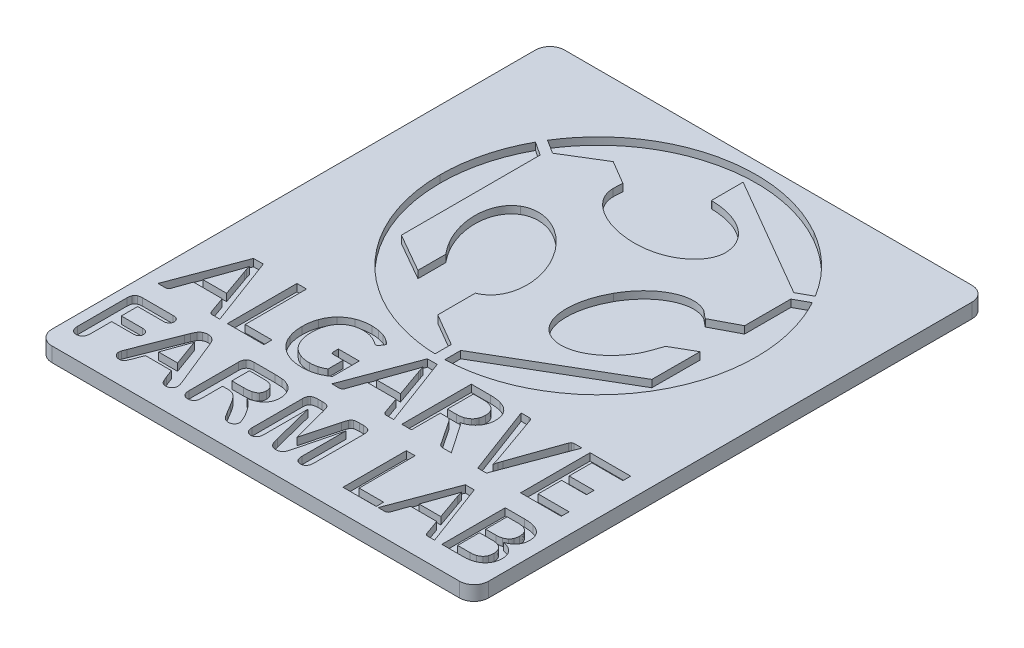
SolidWorks part; units mm, degrees
ref_plane "Front Plane" through (0, 0, 0) normal (0, 0, 1) x (1, 0, 0)
ref_plane "Top Plane" through (0, 0, 0) normal (0, 1, 0) x (1, 0, 0)
ref_plane "Right Plane" through (0, 0, 0) normal (1, 0, 0) x (0, 0, -1)
sketch "Sketch2" plane through (0, 0, 0) normal (0, 1, 0) x (1, 0, 0)
  line L0 (131.5064, 305.804) -> (131.5064, 308.3921)
  line L1 (128.174, 309.6973) -> (128.174, 307.7746)
  line L2 (128.174, 307.7746) -> (125.5144, 309.2966)
  line L3 (125.5144, 309.2966) -> (125.5144, 318.8292)
  line L4 (125.5144, 318.8292) -> (124.5822, 319.4445)
  line L5 (133.7323, 303.3878) -> (133.7333, 304.5062)
  line L6 (133.7333, 304.5062) -> (131.5064, 305.804)
  line L7 (128.4175, 320.9514) -> (130.0431, 319.988)
  line L8 (132.4676, 321.8251) -> (131.2821, 322.5835)
  line L9 (131.2821, 322.5835) -> (134.1018, 324.1923)
  line L10 (134.1018, 324.1923) -> (142.414, 319.3606)
  line L11 (142.414, 319.3606) -> (143.3673, 319.8839)
  line L12 (124.8866, 319.9657) -> (125.8322, 319.3686)
  line L13 (125.8322, 319.3686) -> (128.4175, 320.9514)
  line L14 (142.6945, 315.6997) -> (140.9269, 314.7758)
  line L15 (141.2046, 311.7531) -> (142.7105, 312.6237)
  line L16 (142.7105, 312.6237) -> (142.7015, 309.3183)
  line L17 (142.7015, 309.3183) -> (134.4115, 304.4769)
  line L18 (134.4115, 304.4769) -> (134.4155, 303.3861)
  line L19 (143.648, 319.3955) -> (142.6945, 318.8719)
  line L20 (142.6945, 318.8719) -> (142.6945, 315.6997)
  line L21 (122.4512, 295.9899) -> (120.7008, 295.9899)
  line L22 (120.7008, 295.9899) -> (120.7008, 294.8679)
  line L23 (120.7008, 294.8679) -> (122.1639, 294.8679)
  line L24 (122.1639, 294.2006) -> (120.7008, 294.2006)
  line L25 (120.7008, 294.2006) -> (120.7008, 292.7555)
  line L26 (119.8122, 292.7555) -> (119.8122, 296.1305)
  line L27 (120.3567, 296.675) -> (122.4512, 296.675)
  line L28 (125.88, 292.7854) -> (125.6706, 293.3359)
  line L29 (125.6706, 293.3359) -> (123.8873, 293.3359)
  line L30 (123.8873, 293.3359) -> (123.6779, 292.7734)
  line L31 (122.888, 293.0667) -> (124.01, 295.9151)
  line L32 (125.5479, 295.9211) -> (126.6939, 293.0906)
  line L33 (124.1207, 294.0032) -> (125.4312, 294.0032)
  line L34 (125.4312, 294.0032) -> (124.77, 295.8133)
  line L35 (124.77, 295.8133) -> (124.1207, 294.0032)
  line L36 (128.6716, 294.1647) -> (128.3604, 294.1647)
  line L37 (128.3604, 294.1647) -> (128.3604, 292.7555)
  line L38 (127.4718, 292.7555) -> (127.4718, 296.1305)
  line L39 (128.0163, 296.675) -> (129.4615, 296.675)
  line L40 (130.0689, 292.7794) -> (129.7128, 293.3719)
  line L41 (129.1802, 296.0078) -> (128.3604, 296.0078)
  line L42 (128.3604, 296.0078) -> (128.3604, 294.802)
  line L43 (128.3604, 294.802) -> (129.1563, 294.802)
  line L44 (133.3631, 292.95) -> (132.66, 295.7445)
  line L45 (132.66, 295.7445) -> (132.66, 292.7166)
  line L46 (131.8431, 292.7166) -> (131.8431, 296.1873)
  line L47 (132.3967, 296.675) -> (132.6719, 296.675)
  line L48 (133.3212, 296.0886) -> (133.9585, 293.686)
  line L49 (133.9585, 293.686) -> (134.5958, 296.0886)
  line L50 (135.2451, 296.675) -> (135.5203, 296.675)
  line L51 (136.0739, 296.1873) -> (136.0739, 292.7166)
  line L52 (135.257, 292.7166) -> (135.257, 295.7445)
  line L53 (135.257, 295.7445) -> (134.5539, 292.95)
  line L54 (139.1121, 292.7958) -> (140.7924, 292.7958)
  line L55 (140.7924, 292.7958) -> (140.7924, 292.2887)
  line L56 (140.7924, 292.2887) -> (138.5089, 292.2887)
  line L57 (138.5089, 292.2887) -> (138.5089, 296.6437)
  line L58 (138.5089, 296.6437) -> (139.1121, 296.6437)
  line L59 (139.1121, 296.6437) -> (139.1121, 292.7958)
  line L60 (144.8059, 292.2887) -> (144.3386, 292.2887)
  line L61 (144.1365, 292.4279) -> (143.7653, 293.4752)
  line L62 (143.7653, 293.4752) -> (141.9689, 293.4752)
  line L63 (141.9689, 293.4752) -> (141.6011, 292.4313)
  line L64 (141.3956, 292.2887) -> (140.9283, 292.2887)
  line L65 (140.9283, 292.2887) -> (142.5622, 296.6437)
  line L66 (142.5622, 296.6437) -> (143.1753, 296.6437)
  line L67 (143.1753, 296.6437) -> (144.8059, 292.2887)
  line L68 (142.1214, 293.9061) -> (143.6128, 293.9061)
  line L69 (143.6128, 293.9061) -> (142.9964, 295.6593)
  line L70 (142.7378, 295.656) -> (142.1214, 293.9061)
  line L71 (145.3031, 292.2887) -> (145.3031, 296.6437)
  line L72 (145.3031, 296.6437) -> (146.6321, 296.6437)
  line L73 (146.7746, 292.2887) -> (145.3031, 292.2887)
  line L74 (145.9063, 294.2707) -> (145.9063, 292.766)
  line L75 (145.9063, 292.766) -> (146.7647, 292.766)
  line L76 (146.7647, 294.2707) -> (145.9063, 294.2707)
  line L77 (145.9063, 294.6949) -> (146.6089, 294.6949)
  line L78 (146.6321, 296.1697) -> (145.9063, 296.1697)
  line L79 (145.9063, 296.1697) -> (145.9063, 294.6949)
  line L80 (124.2771, 298.0591) -> (123.7647, 298.0591)
  line L81 (123.543, 298.2117) -> (123.136, 299.3601)
  line L82 (123.136, 299.3601) -> (121.1664, 299.3601)
  line L83 (121.1664, 299.3601) -> (120.763, 298.2153)
  line L84 (120.5377, 298.0591) -> (120.0253, 298.0591)
  line L85 (120.0253, 298.0591) -> (121.8169, 302.8342)
  line L86 (121.8169, 302.8342) -> (122.4892, 302.8342)
  line L87 (122.4892, 302.8342) -> (124.2771, 298.0591)
  line L88 (121.3336, 299.8325) -> (122.9689, 299.8325)
  line L89 (122.9689, 299.8325) -> (122.2929, 301.7549)
  line L90 (122.0095, 301.7513) -> (121.3336, 299.8325)
  line L91 (125.4618, 298.6151) -> (127.3043, 298.6151)
  line L92 (127.3043, 298.6151) -> (127.3043, 298.0591)
  line L93 (127.3043, 298.0591) -> (124.8004, 298.0591)
  line L94 (124.8004, 298.0591) -> (124.8004, 302.8342)
  line L95 (124.8004, 302.8342) -> (125.4618, 302.8342)
  line L96 (125.4618, 302.8342) -> (125.4618, 298.6151)
  line L97 (131.5161, 302.2855) -> (131.3308, 301.9875)
  line L98 (130.9565, 298.8113) -> (130.9565, 299.8579)
  line L99 (130.9565, 299.8579) -> (130.2697, 299.8579)
  line L100 (130.1243, 299.9851) -> (130.1243, 300.3594)
  line L101 (130.1243, 300.3594) -> (131.5561, 300.3594)
  line L102 (131.5561, 300.3594) -> (131.5561, 298.5206)
  line L103 (136.2258, 298.0591) -> (135.7134, 298.0591)
  line L104 (135.4918, 298.2117) -> (135.0848, 299.3601)
  line L105 (135.0848, 299.3601) -> (133.1151, 299.3601)
  line L106 (133.1151, 299.3601) -> (132.7117, 298.2153)
  line L107 (132.4864, 298.0591) -> (131.974, 298.0591)
  line L108 (131.974, 298.0591) -> (133.7656, 302.8342)
  line L109 (133.7656, 302.8342) -> (134.4379, 302.8342)
  line L110 (134.4379, 302.8342) -> (136.2258, 298.0591)
  line L111 (133.2823, 299.8325) -> (134.9176, 299.8325)
  line L112 (134.9176, 299.8325) -> (134.2417, 301.7549)
  line L113 (133.9582, 301.7513) -> (133.2823, 299.8325)
  line L114 (137.4433, 300.0433) -> (137.4433, 298.0591)
  line L115 (137.4433, 298.0591) -> (136.7819, 298.0591)
  line L116 (136.7819, 298.0591) -> (136.7819, 302.8342)
  line L117 (136.7819, 302.8342) -> (138.0901, 302.8342)
  line L118 (138.8969, 299.9488) -> (140.1797, 298.0591)
  line L119 (140.1797, 298.0591) -> (139.591, 298.0591)
  line L120 (139.3257, 298.1935) -> (138.1955, 299.8943)
  line L121 (137.8866, 300.0433) -> (137.4433, 300.0433)
  line L122 (137.4433, 300.5266) -> (138.0647, 300.5266)
  line L123 (138.0901, 302.3145) -> (137.4433, 302.3145)
  line L124 (137.4433, 302.3145) -> (137.4433, 300.5266)
  line L125 (140.2088, 302.8342) -> (140.743, 302.8342)
  line L126 (140.9646, 302.6816) -> (142.1457, 299.3346)
  line L127 (142.4546, 299.3346) -> (143.632, 302.6779)
  line L128 (143.8537, 302.8342) -> (144.3879, 302.8342)
  line L129 (144.3879, 302.8342) -> (142.5963, 298.0591)
  line L130 (142.5963, 298.0591) -> (142.0003, 298.0591)
  line L131 (142.0003, 298.0591) -> (140.2088, 302.8342)
  line L132 (147.7349, 302.8342) -> (147.7349, 302.2964)
  line L133 (147.7349, 302.2964) -> (145.6089, 302.2964)
  line L134 (145.6089, 302.2964) -> (145.6089, 300.7301)
  line L135 (145.6089, 300.7301) -> (147.3206, 300.7301)
  line L136 (147.3206, 300.7301) -> (147.3206, 300.2104)
  line L137 (147.3206, 300.2104) -> (145.6089, 300.2104)
  line L138 (145.6089, 300.2104) -> (145.6089, 298.5969)
  line L139 (145.6089, 298.5969) -> (147.7385, 298.5969)
  line L140 (147.7385, 298.5969) -> (147.7349, 298.0591)
  line L141 (147.7349, 298.0591) -> (144.9439, 298.0591)
  line L142 (144.9439, 298.0591) -> (144.9439, 302.8342)
  line L143 (144.9439, 302.8342) -> (147.7349, 302.8342)
  line L144 (134.1018, 324.1923) -> (134.1018, 302.8342) construction
  line L146 (120.1018, 325.9189) -> (148.1018, 325.9189)
  line L147 (119.1018, 324.9189) -> (119.1018, 291.7017)
  line L148 (120.1018, 290.7017) -> (148.1018, 290.7017)
  line L149 (149.1018, 324.9189) -> (149.1018, 291.7017)
  arc A0 (148.1018, 325.9189) -> (149.1018, 324.9189) centre (148.1018, 324.9189) cw
  arc A1 (148.1018, 290.7017) -> (149.1018, 291.7017) centre (148.1018, 291.7017) ccw
  arc A2 (119.1018, 291.7017) -> (120.1018, 290.7017) centre (120.1018, 291.7017) ccw
  arc A3 (120.1018, 325.9189) -> (119.1018, 324.9189) centre (120.1018, 324.9189) ccw
  spline S0 degree 3 poles (131.5064, 308.3921) (131.5993, 308.4277) (131.6899, 308.4701) (131.7769, 308.5214) knots 0 0 0 0 1 1 1 1
  spline S1 degree 3 poles (131.7769, 308.5214) (133.0109, 309.2489) (133.1406, 311.3156) (132.0664, 313.1373) knots 0 0 0 0 1 1 1 1
  spline S2 degree 3 poles (132.0664, 313.1373) (130.9923, 314.959) (129.1213, 315.846) (127.8874, 315.1185) knots 0 0 0 0 1 1 1 1
  spline S3 degree 3 poles (127.8874, 315.1185) (126.6534, 314.3909) (126.5238, 312.3243) (127.5977, 310.5026) knots 0 0 0 0 1 1 1 1
  spline S4 degree 3 poles (127.5977, 310.5026) (127.771, 310.2088) (127.9652, 309.9397) (128.174, 309.6973) knots 0 0 0 0 1 1 1 1
  spline S5 degree 3 poles (124.5822, 319.4445) (123.733, 317.8973) (123.2501, 316.1206) (123.2501, 314.2311) knots 0 0 0 0 1 1 1 1
  spline S6 degree 3 poles (123.2501, 314.2311) (123.2501, 308.3603) (127.9085, 303.5807) (133.7323, 303.3878) knots 0 0 0 0 1 1 1 1
  spline S7 degree 3 poles (130.0431, 319.988) (130.011, 319.7209) (130.01, 319.4269) (130.011, 319.3258) knots 0 0 0 0 1 1 1 1
  spline S8 degree 3 poles (130.011, 319.3258) (130.0259, 317.8934) (131.9657, 316.8046) (134.0804, 316.8265) knots 0 0 0 0 1 1 1 1
  spline S9 degree 3 poles (134.0804, 316.8265) (136.1951, 316.8484) (137.7012, 318.1295) (137.6905, 319.3899) knots 0 0 0 0 1 1 1 1
  spline S10 degree 3 poles (137.6905, 319.3899) (137.6784, 320.8222) (136.3011, 321.9436) (134.1872, 322.0066) knots 0 0 0 0 1 1 1 1
  spline S11 degree 3 poles (134.1872, 322.0066) (133.4716, 322.028) (132.7817, 321.8851) (132.4676, 321.8251) knots 0 0 0 0 1 1 1 1
  spline S12 degree 3 poles (143.3673, 319.8839) (142.4502, 321.3918) (141.1514, 322.6968) (139.5139, 323.6396) knots 0 0 0 0 1 1 1 1
  spline S13 degree 3 poles (139.5139, 323.6396) (134.426, 326.5689) (127.9596, 324.9166) (124.8866, 319.9657) knots 0 0 0 0 1 1 1 1
  spline S14 degree 3 poles (140.9269, 314.7758) (140.8628, 314.7865) (140.4704, 315.1537) (140.3822, 315.203) knots 0 0 0 0 1 1 1 1
  spline S15 degree 3 poles (140.3822, 315.203) (139.1308, 315.9002) (137.2885, 314.9784) (136.2593, 313.131) knots 0 0 0 0 1 1 1 1
  spline S16 degree 3 poles (136.2593, 313.131) (135.2301, 311.2837) (135.3178, 309.1714) (136.5691, 308.4742) knots 0 0 0 0 1 1 1 1
  spline S17 degree 3 poles (136.5691, 308.4742) (137.8205, 307.7771) (139.6839, 308.6134) (140.7132, 310.4608) knots 0 0 0 0 1 1 1 1
  spline S18 degree 3 poles (140.7132, 310.4608) (140.8792, 310.7588) (141.1009, 311.4506) (141.2046, 311.7531) knots 0 0 0 0 1 1 1 1
  spline S19 degree 3 poles (134.4155, 303.3861) (136.1798, 303.435) (137.9571, 303.9162) (139.5876, 304.8709) knots 0 0 0 0 1 1 1 1
  spline S20 degree 3 poles (139.5876, 304.8709) (144.6537, 307.8374) (146.4243, 314.2724) (143.648, 319.3955) knots 0 0 0 0 1 1 1 1
  spline S21 degree 3 poles (122.1639, 294.8679) (122.2996, 294.8679) (122.4003, 294.8369) (122.4661, 294.7751) knots 0 0 0 0 1 1 1 1
  spline S22 degree 3 poles (122.4661, 294.7751) (122.5339, 294.7153) (122.5679, 294.6345) (122.5679, 294.5328) knots 0 0 0 0 1 1 1 1
  spline S23 degree 3 poles (122.5679, 294.5328) (122.5679, 294.431) (122.5339, 294.3502) (122.4661, 294.2904) knots 0 0 0 0 1 1 1 1
  spline S24 degree 3 poles (122.4661, 294.2904) (122.3983, 294.2306) (122.2976, 294.2006) (122.1639, 294.2006) knots 0 0 0 0 1 1 1 1
  spline S25 degree 3 poles (120.7008, 292.7555) (120.7008, 292.572) (120.6589, 292.4353) (120.5752, 292.3456) knots 0 0 0 0 1 1 1 1
  spline S26 degree 3 poles (120.5752, 292.3456) (120.4934, 292.2578) (120.3877, 292.2139) (120.258, 292.2139) knots 0 0 0 0 1 1 1 1
  spline S27 degree 3 poles (120.258, 292.2139) (120.1264, 292.2139) (120.0187, 292.2588) (119.9349, 292.3486) knots 0 0 0 0 1 1 1 1
  spline S28 degree 3 poles (119.9349, 292.3486) (119.8531, 292.4383) (119.8122, 292.574) (119.8122, 292.7555) knots 0 0 0 0 1 1 1 1
  spline S29 degree 3 poles (119.8122, 296.1305) (119.8122, 296.2582) (119.8312, 296.3619) (119.869, 296.4417) knots 0 0 0 0 1 1 1 1
  spline S30 degree 3 poles (119.869, 296.4417) (119.9069, 296.5235) (119.9658, 296.5823) (120.0456, 296.6182) knots 0 0 0 0 1 1 1 1
  spline S31 degree 3 poles (120.0456, 296.6182) (120.1274, 296.6561) (120.2311, 296.675) (120.3567, 296.675) knots 0 0 0 0 1 1 1 1
  spline S32 degree 3 poles (122.4512, 296.675) (122.5928, 296.675) (122.6975, 296.6431) (122.7653, 296.5793) knots 0 0 0 0 1 1 1 1
  spline S33 degree 3 poles (122.7653, 296.5793) (122.8351, 296.5175) (122.8701, 296.4357) (122.8701, 296.334) knots 0 0 0 0 1 1 1 1
  spline S34 degree 3 poles (122.8701, 296.334) (122.8701, 296.2302) (122.8351, 296.1465) (122.7653, 296.0826) knots 0 0 0 0 1 1 1 1
  spline S35 degree 3 poles (122.7653, 296.0826) (122.6975, 296.0208) (122.5928, 295.9899) (122.4512, 295.9899) knots 0 0 0 0 1 1 1 1
  spline S36 degree 3 poles (123.6779, 292.7734) (123.5961, 292.554) (123.5263, 292.4054) (123.4685, 292.3276) knots 0 0 0 0 1 1 1 1
  spline S37 degree 3 poles (123.4685, 292.3276) (123.4106, 292.2518) (123.3159, 292.2139) (123.1842, 292.2139) knots 0 0 0 0 1 1 1 1
  spline S38 degree 3 poles (123.1842, 292.2139) (123.0725, 292.2139) (122.9738, 292.2548) (122.888, 292.3366) knots 0 0 0 0 1 1 1 1
  spline S39 degree 3 poles (122.888, 292.3366) (122.8022, 292.4184) (122.7593, 292.5111) (122.7593, 292.6149) knots 0 0 0 0 1 1 1 1
  spline S40 degree 3 poles (122.7593, 292.6149) (122.7593, 292.6747) (122.7693, 292.7365) (122.7893, 292.8004) knots 0 0 0 0 1 1 1 1
  spline S41 degree 3 poles (122.7893, 292.8004) (122.8092, 292.8642) (122.8421, 292.953) (122.888, 293.0667) knots 0 0 0 0 1 1 1 1
  spline S42 degree 3 poles (124.01, 295.9151) (124.0419, 295.9969) (124.0798, 296.0946) (124.1237, 296.2083) knots 0 0 0 0 1 1 1 1
  spline S43 degree 3 poles (124.1237, 296.2083) (124.1696, 296.324) (124.2175, 296.4197) (124.2673, 296.4955) knots 0 0 0 0 1 1 1 1
  spline S44 degree 3 poles (124.2673, 296.4955) (124.3192, 296.5713) (124.386, 296.6322) (124.4678, 296.678) knots 0 0 0 0 1 1 1 1
  spline S45 degree 3 poles (124.4678, 296.678) (124.5516, 296.7259) (124.6543, 296.7498) (124.776, 296.7498) knots 0 0 0 0 1 1 1 1
  spline S46 degree 3 poles (124.776, 296.7498) (124.8996, 296.7498) (125.0024, 296.7259) (125.0842, 296.678) knots 0 0 0 0 1 1 1 1
  spline S47 degree 3 poles (125.0842, 296.678) (125.1679, 296.6322) (125.2347, 296.5723) (125.2846, 296.4985) knots 0 0 0 0 1 1 1 1
  spline S48 degree 3 poles (125.2846, 296.4985) (125.3365, 296.4247) (125.3794, 296.3449) (125.4133, 296.2592) knots 0 0 0 0 1 1 1 1
  spline S49 degree 3 poles (125.4133, 296.2592) (125.4492, 296.1754) (125.4941, 296.0627) (125.5479, 295.9211) knots 0 0 0 0 1 1 1 1
  spline S50 degree 3 poles (126.6939, 293.0906) (126.7836, 292.8752) (126.8285, 292.7186) (126.8285, 292.6209) knots 0 0 0 0 1 1 1 1
  spline S51 degree 3 poles (126.8285, 292.6209) (126.8285, 292.5191) (126.7856, 292.4254) (126.6998, 292.3396) knots 0 0 0 0 1 1 1 1
  spline S52 degree 3 poles (126.6998, 292.3396) (126.6161, 292.2558) (126.5143, 292.2139) (126.3947, 292.2139) knots 0 0 0 0 1 1 1 1
  spline S53 degree 3 poles (126.3947, 292.2139) (126.3248, 292.2139) (126.265, 292.2269) (126.2151, 292.2528) knots 0 0 0 0 1 1 1 1
  spline S54 degree 3 poles (126.2151, 292.2528) (126.1653, 292.2768) (126.1234, 292.3097) (126.0895, 292.3516) knots 0 0 0 0 1 1 1 1
  spline S55 degree 3 poles (126.0895, 292.3516) (126.0556, 292.3955) (126.0187, 292.4613) (125.9788, 292.549) knots 0 0 0 0 1 1 1 1
  spline S56 degree 3 poles (125.9788, 292.549) (125.9409, 292.6388) (125.908, 292.7176) (125.88, 292.7854) knots 0 0 0 0 1 1 1 1
  spline S57 degree 3 poles (128.3604, 292.7555) (128.3604, 292.57) (128.3195, 292.4334) (128.2377, 292.3456) knots 0 0 0 0 1 1 1 1
  spline S58 degree 3 poles (128.2377, 292.3456) (128.156, 292.2578) (128.0492, 292.2139) (127.9176, 292.2139) knots 0 0 0 0 1 1 1 1
  spline S59 degree 3 poles (127.9176, 292.2139) (127.776, 292.2139) (127.6663, 292.2598) (127.5885, 292.3516) knots 0 0 0 0 1 1 1 1
  spline S60 degree 3 poles (127.5885, 292.3516) (127.5107, 292.4433) (127.4718, 292.578) (127.4718, 292.7555) knots 0 0 0 0 1 1 1 1
  spline S61 degree 3 poles (127.4718, 296.1305) (127.4718, 296.322) (127.5147, 296.4606) (127.6004, 296.5464) knots 0 0 0 0 1 1 1 1
  spline S62 degree 3 poles (127.6004, 296.5464) (127.6862, 296.6322) (127.8248, 296.675) (128.0163, 296.675) knots 0 0 0 0 1 1 1 1
  spline S63 degree 3 poles (129.4615, 296.675) (129.661, 296.675) (129.8315, 296.6661) (129.9731, 296.6481) knots 0 0 0 0 1 1 1 1
  spline S64 degree 3 poles (129.9731, 296.6481) (130.1147, 296.6322) (130.2424, 296.5983) (130.3561, 296.5464) knots 0 0 0 0 1 1 1 1
  spline S65 degree 3 poles (130.3561, 296.5464) (130.4937, 296.4885) (130.6154, 296.4058) (130.7211, 296.2981) knots 0 0 0 0 1 1 1 1
  spline S66 degree 3 poles (130.7211, 296.2981) (130.8268, 296.1903) (130.9066, 296.0647) (130.9605, 295.9211) knots 0 0 0 0 1 1 1 1
  spline S67 degree 3 poles (130.9605, 295.9211) (131.0163, 295.7794) (131.0443, 295.6288) (131.0443, 295.4693) knots 0 0 0 0 1 1 1 1
  spline S68 degree 3 poles (131.0443, 295.4693) (131.0443, 295.1421) (130.9515, 294.8808) (130.766, 294.6854) knots 0 0 0 0 1 1 1 1
  spline S69 degree 3 poles (130.766, 294.6854) (130.5825, 294.4899) (130.3032, 294.3512) (129.9282, 294.2695) knots 0 0 0 0 1 1 1 1
  spline S70 degree 3 poles (129.9282, 294.2695) (130.0858, 294.1857) (130.2364, 294.062) (130.38, 293.8984) knots 0 0 0 0 1 1 1 1
  spline S71 degree 3 poles (130.38, 293.8984) (130.5237, 293.7349) (130.6513, 293.5603) (130.763, 293.3748) knots 0 0 0 0 1 1 1 1
  spline S72 degree 3 poles (130.763, 293.3748) (130.8767, 293.1913) (130.9645, 293.0248) (131.0263, 292.8752) knots 0 0 0 0 1 1 1 1
  spline S73 degree 3 poles (131.0263, 292.8752) (131.0901, 292.7276) (131.1221, 292.6258) (131.1221, 292.57) knots 0 0 0 0 1 1 1 1
  spline S74 degree 3 poles (131.1221, 292.57) (131.1221, 292.5121) (131.1031, 292.4543) (131.0652, 292.3965) knots 0 0 0 0 1 1 1 1
  spline S75 degree 3 poles (131.0652, 292.3965) (131.0293, 292.3406) (130.9794, 292.2967) (130.9156, 292.2648) knots 0 0 0 0 1 1 1 1
  spline S76 degree 3 poles (130.9156, 292.2648) (130.8518, 292.2309) (130.778, 292.2139) (130.6942, 292.2139) knots 0 0 0 0 1 1 1 1
  spline S77 degree 3 poles (130.6942, 292.2139) (130.5945, 292.2139) (130.5107, 292.2379) (130.4429, 292.2857) knots 0 0 0 0 1 1 1 1
  spline S78 degree 3 poles (130.4429, 292.2857) (130.3751, 292.3316) (130.3162, 292.3905) (130.2663, 292.4623) knots 0 0 0 0 1 1 1 1
  spline S79 degree 3 poles (130.2663, 292.4623) (130.2185, 292.5341) (130.1526, 292.6398) (130.0689, 292.7794) knots 0 0 0 0 1 1 1 1
  spline S80 degree 3 poles (129.7128, 293.3719) (129.5852, 293.5893) (129.4705, 293.7548) (129.3687, 293.8685) knots 0 0 0 0 1 1 1 1
  spline S81 degree 3 poles (129.3687, 293.8685) (129.269, 293.9822) (129.1673, 294.06) (129.0635, 294.1019) knots 0 0 0 0 1 1 1 1
  spline S82 degree 3 poles (129.0635, 294.1019) (128.9598, 294.1438) (128.8292, 294.1647) (128.6716, 294.1647) knots 0 0 0 0 1 1 1 1
  spline S83 degree 3 poles (129.1563, 294.802) (129.3697, 294.802) (129.5493, 294.82) (129.6949, 294.8559) knots 0 0 0 0 1 1 1 1
  spline S84 degree 3 poles (129.6949, 294.8559) (129.8405, 294.8938) (129.9512, 294.9566) (130.027, 295.0444) knots 0 0 0 0 1 1 1 1
  spline S85 degree 3 poles (130.027, 295.0444) (130.1048, 295.1342) (130.1437, 295.2568) (130.1437, 295.4124) knots 0 0 0 0 1 1 1 1
  spline S86 degree 3 poles (130.1437, 295.4124) (130.1437, 295.5341) (130.1128, 295.6408) (130.0509, 295.7326) knots 0 0 0 0 1 1 1 1
  spline S87 degree 3 poles (130.0509, 295.7326) (129.9891, 295.8263) (129.9033, 295.8961) (129.7936, 295.942) knots 0 0 0 0 1 1 1 1
  spline S88 degree 3 poles (129.7936, 295.942) (129.6899, 295.9859) (129.4854, 296.0078) (129.1802, 296.0078) knots 0 0 0 0 1 1 1 1
  spline S89 degree 3 poles (132.66, 292.7166) (132.66, 292.549) (132.6221, 292.4234) (132.5463, 292.3396) knots 0 0 0 0 1 1 1 1
  spline S90 degree 3 poles (132.5463, 292.3396) (132.4725, 292.2558) (132.3737, 292.2139) (132.2501, 292.2139) knots 0 0 0 0 1 1 1 1
  spline S91 degree 3 poles (132.2501, 292.2139) (132.1304, 292.2139) (132.0326, 292.2548) (131.9568, 292.3366) knots 0 0 0 0 1 1 1 1
  spline S92 degree 3 poles (131.9568, 292.3366) (131.881, 292.4204) (131.8431, 292.547) (131.8431, 292.7166) knots 0 0 0 0 1 1 1 1
  spline S93 degree 3 poles (131.8431, 296.1873) (131.8431, 296.3788) (131.893, 296.5075) (131.9927, 296.5733) knots 0 0 0 0 1 1 1 1
  spline S94 degree 3 poles (131.9927, 296.5733) (132.0925, 296.6411) (132.2271, 296.675) (132.3967, 296.675) knots 0 0 0 0 1 1 1 1
  spline S95 degree 3 poles (132.6719, 296.675) (132.8375, 296.675) (132.9572, 296.6601) (133.031, 296.6302) knots 0 0 0 0 1 1 1 1
  spline S96 degree 3 poles (133.031, 296.6302) (133.1068, 296.6002) (133.1626, 296.5464) (133.1985, 296.4686) knots 0 0 0 0 1 1 1 1
  spline S97 degree 3 poles (133.1985, 296.4686) (133.2344, 296.3908) (133.2753, 296.2641) (133.3212, 296.0886) knots 0 0 0 0 1 1 1 1
  spline S98 degree 3 poles (134.5958, 296.0886) (134.6417, 296.2641) (134.6826, 296.3908) (134.7185, 296.4686) knots 0 0 0 0 1 1 1 1
  spline S99 degree 3 poles (134.7185, 296.4686) (134.7544, 296.5464) (134.8092, 296.6002) (134.883, 296.6302) knots 0 0 0 0 1 1 1 1
  spline S100 degree 3 poles (134.883, 296.6302) (134.9588, 296.6601) (135.0795, 296.675) (135.2451, 296.675) knots 0 0 0 0 1 1 1 1
  spline S101 degree 3 poles (135.5203, 296.675) (135.6899, 296.675) (135.8245, 296.6411) (135.9243, 296.5733) knots 0 0 0 0 1 1 1 1
  spline S102 degree 3 poles (135.9243, 296.5733) (136.024, 296.5075) (136.0739, 296.3788) (136.0739, 296.1873) knots 0 0 0 0 1 1 1 1
  spline S103 degree 3 poles (136.0739, 292.7166) (136.0739, 292.549) (136.036, 292.4234) (135.9602, 292.3396) knots 0 0 0 0 1 1 1 1
  spline S104 degree 3 poles (135.9602, 292.3396) (135.8864, 292.2558) (135.7866, 292.2139) (135.661, 292.2139) knots 0 0 0 0 1 1 1 1
  spline S105 degree 3 poles (135.661, 292.2139) (135.5433, 292.2139) (135.4465, 292.2558) (135.3707, 292.3396) knots 0 0 0 0 1 1 1 1
  spline S106 degree 3 poles (135.3707, 292.3396) (135.2949, 292.4234) (135.257, 292.549) (135.257, 292.7166) knots 0 0 0 0 1 1 1 1
  spline S107 degree 3 poles (134.5539, 292.95) (134.508, 292.7685) (134.4701, 292.6348) (134.4402, 292.549) knots 0 0 0 0 1 1 1 1
  spline S108 degree 3 poles (134.4402, 292.549) (134.4123, 292.4653) (134.3594, 292.3885) (134.2816, 292.3187) knots 0 0 0 0 1 1 1 1
  spline S109 degree 3 poles (134.2816, 292.3187) (134.2038, 292.2488) (134.0961, 292.2139) (133.9585, 292.2139) knots 0 0 0 0 1 1 1 1
  spline S110 degree 3 poles (133.9585, 292.2139) (133.8548, 292.2139) (133.767, 292.2369) (133.6952, 292.2828) knots 0 0 0 0 1 1 1 1
  spline S111 degree 3 poles (133.6952, 292.2828) (133.6234, 292.3266) (133.5675, 292.3835) (133.5276, 292.4533) knots 0 0 0 0 1 1 1 1
  spline S112 degree 3 poles (133.5276, 292.4533) (133.4878, 292.5231) (133.4558, 292.5999) (133.4319, 292.6837) knots 0 0 0 0 1 1 1 1
  spline S113 degree 3 poles (133.4319, 292.6837) (133.41, 292.7695) (133.387, 292.8582) (133.3631, 292.95) knots 0 0 0 0 1 1 1 1
  spline S114 degree 3 poles (144.3386, 292.2887) (144.2856, 292.2887) (144.2425, 292.302) (144.2094, 292.3285) knots 0 0 0 0 1 1 1 1
  spline S115 degree 3 poles (144.2094, 292.3285) (144.1784, 292.355) (144.1541, 292.3882) (144.1365, 292.4279) knots 0 0 0 0 1 1 1 1
  spline S116 degree 3 poles (141.6011, 292.4313) (141.5878, 292.3937) (141.5624, 292.3605) (141.5248, 292.3318) knots 0 0 0 0 1 1 1 1
  spline S117 degree 3 poles (141.5248, 292.3318) (141.4895, 292.3031) (141.4464, 292.2887) (141.3956, 292.2887) knots 0 0 0 0 1 1 1 1
  spline S118 degree 3 poles (142.9964, 295.6593) (142.9743, 295.7124) (142.9522, 295.7742) (142.9301, 295.8449) knots 0 0 0 0 1 1 1 1
  spline S119 degree 3 poles (142.9301, 295.8449) (142.908, 295.9156) (142.887, 295.9919) (142.8671, 296.0736) knots 0 0 0 0 1 1 1 1
  spline S120 degree 3 poles (142.8671, 296.0736) (142.845, 295.9896) (142.8229, 295.9123) (142.8008, 295.8416) knots 0 0 0 0 1 1 1 1
  spline S121 degree 3 poles (142.8008, 295.8416) (142.7787, 295.7709) (142.7577, 295.709) (142.7378, 295.656) knots 0 0 0 0 1 1 1 1
  spline S122 degree 3 poles (146.6321, 296.6437) (146.8884, 296.6437) (147.1082, 296.6171) (147.2916, 296.5641) knots 0 0 0 0 1 1 1 1
  spline S123 degree 3 poles (147.2916, 296.5641) (147.4772, 296.5133) (147.6286, 296.4382) (147.7457, 296.3387) knots 0 0 0 0 1 1 1 1
  spline S124 degree 3 poles (147.7457, 296.3387) (147.865, 296.2415) (147.9523, 296.1222) (148.0075, 295.9808) knots 0 0 0 0 1 1 1 1
  spline S125 degree 3 poles (148.0075, 295.9808) (148.0627, 295.8416) (148.0903, 295.6836) (148.0903, 295.5069) knots 0 0 0 0 1 1 1 1
  spline S126 degree 3 poles (148.0903, 295.5069) (148.0903, 295.4008) (148.0738, 295.2981) (148.0406, 295.1986) knots 0 0 0 0 1 1 1 1
  spline S127 degree 3 poles (148.0406, 295.1986) (148.0097, 295.0992) (147.9622, 295.0075) (147.8981, 294.9236) knots 0 0 0 0 1 1 1 1
  spline S128 degree 3 poles (147.8981, 294.9236) (147.834, 294.8396) (147.7534, 294.7634) (147.6562, 294.6949) knots 0 0 0 0 1 1 1 1
  spline S129 degree 3 poles (147.6562, 294.6949) (147.559, 294.6264) (147.4441, 294.5711) (147.3115, 294.5292) knots 0 0 0 0 1 1 1 1
  spline S130 degree 3 poles (147.3115, 294.5292) (147.6142, 294.4695) (147.8418, 294.3557) (147.9942, 294.1878) knots 0 0 0 0 1 1 1 1
  spline S131 degree 3 poles (147.9942, 294.1878) (148.1489, 294.0221) (148.2262, 293.8033) (148.2262, 293.5316) knots 0 0 0 0 1 1 1 1
  spline S132 degree 3 poles (148.2262, 293.5316) (148.2262, 293.346) (148.1942, 293.177) (148.1301, 293.0245) knots 0 0 0 0 1 1 1 1
  spline S133 degree 3 poles (148.1301, 293.0245) (148.066, 292.872) (147.9721, 292.7406) (147.8484, 292.6301) knots 0 0 0 0 1 1 1 1
  spline S134 degree 3 poles (147.8484, 292.6301) (147.7247, 292.5218) (147.5722, 292.4379) (147.391, 292.3782) knots 0 0 0 0 1 1 1 1
  spline S135 degree 3 poles (147.391, 292.3782) (147.2121, 292.3186) (147.0066, 292.2887) (146.7746, 292.2887) knots 0 0 0 0 1 1 1 1
  spline S136 degree 3 poles (146.7647, 292.766) (146.9171, 292.766) (147.0475, 292.7848) (147.1557, 292.8223) knots 0 0 0 0 1 1 1 1
  spline S137 degree 3 poles (147.1557, 292.8223) (147.2662, 292.8621) (147.3557, 292.9162) (147.4242, 292.9847) knots 0 0 0 0 1 1 1 1
  spline S138 degree 3 poles (147.4242, 292.9847) (147.4949, 293.0532) (147.5457, 293.135) (147.5766, 293.23) knots 0 0 0 0 1 1 1 1
  spline S139 degree 3 poles (147.5766, 293.23) (147.6098, 293.3272) (147.6264, 293.4322) (147.6264, 293.5448) knots 0 0 0 0 1 1 1 1
  spline S140 degree 3 poles (147.6264, 293.5448) (147.6264, 293.768) (147.5557, 293.9448) (147.4142, 294.0751) knots 0 0 0 0 1 1 1 1
  spline S141 degree 3 poles (147.4142, 294.0751) (147.275, 294.2055) (147.0585, 294.2707) (146.7647, 294.2707) knots 0 0 0 0 1 1 1 1
  spline S142 degree 3 poles (146.6089, 294.6949) (146.7569, 294.6949) (146.8862, 294.7126) (146.9966, 294.7479) knots 0 0 0 0 1 1 1 1
  spline S143 degree 3 poles (146.9966, 294.7479) (147.1071, 294.7855) (147.1988, 294.8363) (147.2717, 294.9004) knots 0 0 0 0 1 1 1 1
  spline S144 degree 3 poles (147.2717, 294.9004) (147.3446, 294.9644) (147.3988, 295.0418) (147.4341, 295.1324) knots 0 0 0 0 1 1 1 1
  spline S145 degree 3 poles (147.4341, 295.1324) (147.4717, 295.2229) (147.4905, 295.3235) (147.4905, 295.434) knots 0 0 0 0 1 1 1 1
  spline S146 degree 3 poles (147.4905, 295.434) (147.4905, 295.688) (147.4209, 295.8736) (147.2817, 295.9907) knots 0 0 0 0 1 1 1 1
  spline S147 degree 3 poles (147.2817, 295.9907) (147.1447, 296.1101) (146.9282, 296.1697) (146.6321, 296.1697) knots 0 0 0 0 1 1 1 1
  spline S148 degree 3 poles (123.7647, 298.0591) (123.7066, 298.0591) (123.6593, 298.0736) (123.623, 298.1027) knots 0 0 0 0 1 1 1 1
  spline S149 degree 3 poles (123.623, 298.1027) (123.5891, 298.1318) (123.5624, 298.1681) (123.543, 298.2117) knots 0 0 0 0 1 1 1 1
  spline S150 degree 3 poles (120.763, 298.2153) (120.7485, 298.1742) (120.7206, 298.1378) (120.6794, 298.1063) knots 0 0 0 0 1 1 1 1
  spline S151 degree 3 poles (120.6794, 298.1063) (120.6407, 298.0748) (120.5934, 298.0591) (120.5377, 298.0591) knots 0 0 0 0 1 1 1 1
  spline S152 degree 3 poles (122.2929, 301.7549) (122.2687, 301.813) (122.2445, 301.8809) (122.2203, 301.9584) knots 0 0 0 0 1 1 1 1
  spline S153 degree 3 poles (122.2203, 301.9584) (122.196, 302.0359) (122.173, 302.1195) (122.1512, 302.2091) knots 0 0 0 0 1 1 1 1
  spline S154 degree 3 poles (122.1512, 302.2091) (122.127, 302.1171) (122.1028, 302.0323) (122.0785, 301.9548) knots 0 0 0 0 1 1 1 1
  spline S155 degree 3 poles (122.0785, 301.9548) (122.0543, 301.8772) (122.0313, 301.8094) (122.0095, 301.7513) knots 0 0 0 0 1 1 1 1
  spline S156 degree 3 poles (131.5561, 298.5206) (131.3235, 298.3486) (131.0752, 298.2202) (130.8111, 298.1354) knots 0 0 0 0 1 1 1 1
  spline S157 degree 3 poles (130.8111, 298.1354) (130.5495, 298.0506) (130.2648, 298.0082) (129.9571, 298.0082) knots 0 0 0 0 1 1 1 1
  spline S158 degree 3 poles (129.9571, 298.0082) (129.5865, 298.0082) (129.2509, 298.0676) (128.9505, 298.1863) knots 0 0 0 0 1 1 1 1
  spline S159 degree 3 poles (128.9505, 298.1863) (128.6525, 298.305) (128.3981, 298.4709) (128.1874, 298.6841) knots 0 0 0 0 1 1 1 1
  spline S160 degree 3 poles (128.1874, 298.6841) (127.9766, 298.8997) (127.8143, 299.1566) (127.7004, 299.4545) knots 0 0 0 0 1 1 1 1
  spline S161 degree 3 poles (127.7004, 299.4545) (127.5865, 299.755) (127.5296, 300.0857) (127.5296, 300.4466) knots 0 0 0 0 1 1 1 1
  spline S162 degree 3 poles (127.5296, 300.4466) (127.5296, 300.81) (127.5841, 301.1407) (127.6931, 301.4387) knots 0 0 0 0 1 1 1 1
  spline S163 degree 3 poles (127.6931, 301.4387) (127.8046, 301.7391) (127.962, 301.996) (128.1655, 302.2091) knots 0 0 0 0 1 1 1 1
  spline S164 degree 3 poles (128.1655, 302.2091) (128.3715, 302.4248) (128.6198, 302.5919) (128.9105, 302.7106) knots 0 0 0 0 1 1 1 1
  spline S165 degree 3 poles (128.9105, 302.7106) (129.2012, 302.8294) (129.5271, 302.8887) (129.8881, 302.8887) knots 0 0 0 0 1 1 1 1
  spline S166 degree 3 poles (129.8881, 302.8887) (130.0722, 302.8887) (130.2418, 302.8742) (130.3968, 302.8451) knots 0 0 0 0 1 1 1 1
  spline S167 degree 3 poles (130.3968, 302.8451) (130.5543, 302.8185) (130.6997, 302.7785) (130.8329, 302.7252) knots 0 0 0 0 1 1 1 1
  spline S168 degree 3 poles (130.8329, 302.7252) (130.9662, 302.6743) (131.0885, 302.6113) (131.2, 302.5362) knots 0 0 0 0 1 1 1 1
  spline S169 degree 3 poles (131.2, 302.5362) (131.3138, 302.4611) (131.4192, 302.3775) (131.5161, 302.2855) knots 0 0 0 0 1 1 1 1
  spline S170 degree 3 poles (131.3308, 301.9875) (131.3017, 301.939) (131.263, 301.9087) (131.2145, 301.8966) knots 0 0 0 0 1 1 1 1
  spline S171 degree 3 poles (131.2145, 301.8966) (131.1661, 301.8845) (131.114, 301.8954) (131.0582, 301.9293) knots 0 0 0 0 1 1 1 1
  spline S172 degree 3 poles (131.0582, 301.9293) (131.0025, 301.9608) (130.9407, 301.9984) (130.8729, 302.042) knots 0 0 0 0 1 1 1 1
  spline S173 degree 3 poles (130.8729, 302.042) (130.8075, 302.088) (130.7288, 302.1304) (130.6367, 302.1692) knots 0 0 0 0 1 1 1 1
  spline S174 degree 3 poles (130.6367, 302.1692) (130.5446, 302.2104) (130.4356, 302.2455) (130.3096, 302.2746) knots 0 0 0 0 1 1 1 1
  spline S175 degree 3 poles (130.3096, 302.2746) (130.1837, 302.3036) (130.0347, 302.3182) (129.8626, 302.3182) knots 0 0 0 0 1 1 1 1
  spline S176 degree 3 poles (129.8626, 302.3182) (129.6107, 302.3182) (129.3817, 302.2746) (129.1758, 302.1873) knots 0 0 0 0 1 1 1 1
  spline S177 degree 3 poles (129.1758, 302.1873) (128.9723, 302.1001) (128.7979, 301.9754) (128.6525, 301.813) knots 0 0 0 0 1 1 1 1
  spline S178 degree 3 poles (128.6525, 301.813) (128.5096, 301.6507) (128.3993, 301.4533) (128.3218, 301.2207) knots 0 0 0 0 1 1 1 1
  spline S179 degree 3 poles (128.3218, 301.2207) (128.2443, 300.9905) (128.2055, 300.7325) (128.2055, 300.4466) knots 0 0 0 0 1 1 1 1
  spline S180 degree 3 poles (128.2055, 300.4466) (128.2055, 300.1486) (128.2455, 299.8809) (128.3254, 299.6435) knots 0 0 0 0 1 1 1 1
  spline S181 degree 3 poles (128.3254, 299.6435) (128.4078, 299.4085) (128.5241, 299.2086) (128.6743, 299.0439) knots 0 0 0 0 1 1 1 1
  spline S182 degree 3 poles (128.6743, 299.0439) (128.8269, 298.8816) (129.0099, 298.7568) (129.2231, 298.6696) knots 0 0 0 0 1 1 1 1
  spline S183 degree 3 poles (129.2231, 298.6696) (129.4362, 298.5848) (129.6749, 298.5424) (129.939, 298.5424) knots 0 0 0 0 1 1 1 1
  spline S184 degree 3 poles (129.939, 298.5424) (130.1425, 298.5424) (130.3242, 298.5654) (130.4841, 298.6114) knots 0 0 0 0 1 1 1 1
  spline S185 degree 3 poles (130.4841, 298.6114) (130.644, 298.6599) (130.8014, 298.7265) (130.9565, 298.8113) knots 0 0 0 0 1 1 1 1
  spline S186 degree 3 poles (130.2697, 299.8579) (130.226, 299.8579) (130.1909, 299.87) (130.1643, 299.8943) knots 0 0 0 0 1 1 1 1
  spline S187 degree 3 poles (130.1643, 299.8943) (130.1376, 299.9185) (130.1243, 299.9488) (130.1243, 299.9851) knots 0 0 0 0 1 1 1 1
  spline S188 degree 3 poles (135.7134, 298.0591) (135.6553, 298.0591) (135.6081, 298.0736) (135.5717, 298.1027) knots 0 0 0 0 1 1 1 1
  spline S189 degree 3 poles (135.5717, 298.1027) (135.5378, 298.1318) (135.5112, 298.1681) (135.4918, 298.2117) knots 0 0 0 0 1 1 1 1
  spline S190 degree 3 poles (132.7117, 298.2153) (132.6972, 298.1742) (132.6693, 298.1378) (132.6281, 298.1063) knots 0 0 0 0 1 1 1 1
  spline S191 degree 3 poles (132.6281, 298.1063) (132.5894, 298.0748) (132.5421, 298.0591) (132.4864, 298.0591) knots 0 0 0 0 1 1 1 1
  spline S192 degree 3 poles (134.2417, 301.7549) (134.2174, 301.813) (134.1932, 301.8809) (134.169, 301.9584) knots 0 0 0 0 1 1 1 1
  spline S193 degree 3 poles (134.169, 301.9584) (134.1448, 302.0359) (134.1217, 302.1195) (134.0999, 302.2091) knots 0 0 0 0 1 1 1 1
  spline S194 degree 3 poles (134.0999, 302.2091) (134.0757, 302.1171) (134.0515, 302.0323) (134.0273, 301.9548) knots 0 0 0 0 1 1 1 1
  spline S195 degree 3 poles (134.0273, 301.9548) (134.003, 301.8772) (133.98, 301.8094) (133.9582, 301.7513) knots 0 0 0 0 1 1 1 1
  spline S196 degree 3 poles (138.0901, 302.8342) (138.3808, 302.8342) (138.6316, 302.8027) (138.8424, 302.7397) knots 0 0 0 0 1 1 1 1
  spline S197 degree 3 poles (138.8424, 302.7397) (139.0556, 302.6792) (139.23, 302.5907) (139.3657, 302.4744) knots 0 0 0 0 1 1 1 1
  spline S198 degree 3 poles (139.3657, 302.4744) (139.5038, 302.3606) (139.6055, 302.2213) (139.6709, 302.0565) knots 0 0 0 0 1 1 1 1
  spline S199 degree 3 poles (139.6709, 302.0565) (139.7363, 301.8942) (139.769, 301.7113) (139.769, 301.5078) knots 0 0 0 0 1 1 1 1
  spline S200 degree 3 poles (139.769, 301.5078) (139.769, 301.3406) (139.7436, 301.1843) (139.6927, 301.039) knots 0 0 0 0 1 1 1 1
  spline S201 degree 3 poles (139.6927, 301.039) (139.6443, 300.8936) (139.5728, 300.7628) (139.4783, 300.6465) knots 0 0 0 0 1 1 1 1
  spline S202 degree 3 poles (139.4783, 300.6465) (139.3863, 300.5302) (139.2724, 300.4297) (139.1367, 300.3449) knots 0 0 0 0 1 1 1 1
  spline S203 degree 3 poles (139.1367, 300.3449) (139.001, 300.2625) (138.8472, 300.1995) (138.6752, 300.1559) knots 0 0 0 0 1 1 1 1
  spline S204 degree 3 poles (138.6752, 300.1559) (138.7164, 300.1293) (138.7551, 300.099) (138.7915, 300.0651) knots 0 0 0 0 1 1 1 1
  spline S205 degree 3 poles (138.7915, 300.0651) (138.8278, 300.0336) (138.863, 299.9948) (138.8969, 299.9488) knots 0 0 0 0 1 1 1 1
  spline S206 degree 3 poles (139.591, 298.0591) (139.4771, 298.0591) (139.3887, 298.1039) (139.3257, 298.1935) knots 0 0 0 0 1 1 1 1
  spline S207 degree 3 poles (138.1955, 299.8943) (138.1592, 299.9476) (138.1192, 299.9851) (138.0756, 300.0069) knots 0 0 0 0 1 1 1 1
  spline S208 degree 3 poles (138.0756, 300.0069) (138.0344, 300.0311) (137.9714, 300.0433) (137.8866, 300.0433) knots 0 0 0 0 1 1 1 1
  spline S209 degree 3 poles (138.0647, 300.5266) (138.2391, 300.5266) (138.3917, 300.5484) (138.5226, 300.592) knots 0 0 0 0 1 1 1 1
  spline S210 degree 3 poles (138.5226, 300.592) (138.6558, 300.638) (138.7673, 300.7022) (138.8569, 300.7846) knots 0 0 0 0 1 1 1 1
  spline S211 degree 3 poles (138.8569, 300.7846) (138.9465, 300.867) (139.0132, 300.9651) (139.0568, 301.079) knots 0 0 0 0 1 1 1 1
  spline S212 degree 3 poles (139.0568, 301.079) (139.1028, 301.1953) (139.1258, 301.3224) (139.1258, 301.4605) knots 0 0 0 0 1 1 1 1
  spline S213 degree 3 poles (139.1258, 301.4605) (139.1258, 302.0299) (138.7806, 302.3145) (138.0901, 302.3145) knots 0 0 0 0 1 1 1 1
  spline S214 degree 3 poles (140.743, 302.8342) (140.8011, 302.8342) (140.8483, 302.8197) (140.8847, 302.7906) knots 0 0 0 0 1 1 1 1
  spline S215 degree 3 poles (140.8847, 302.7906) (140.921, 302.7615) (140.9477, 302.7252) (140.9646, 302.6816) knots 0 0 0 0 1 1 1 1
  spline S216 degree 3 poles (142.1457, 299.3346) (142.1748, 299.2595) (142.2026, 299.1771) (142.2293, 299.0875) knots 0 0 0 0 1 1 1 1
  spline S217 degree 3 poles (142.2293, 299.0875) (142.2584, 299.0003) (142.2838, 298.9082) (142.3056, 298.8113) knots 0 0 0 0 1 1 1 1
  spline S218 degree 3 poles (142.3056, 298.8113) (142.325, 298.9082) (142.3468, 299.0003) (142.371, 299.0875) knots 0 0 0 0 1 1 1 1
  spline S219 degree 3 poles (142.371, 299.0875) (142.3977, 299.1771) (142.4255, 299.2595) (142.4546, 299.3346) knots 0 0 0 0 1 1 1 1
  spline S220 degree 3 poles (143.632, 302.6779) (143.6466, 302.7191) (143.6732, 302.7555) (143.712, 302.787) knots 0 0 0 0 1 1 1 1
  spline S221 degree 3 poles (143.712, 302.787) (143.7507, 302.8185) (143.798, 302.8342) (143.8537, 302.8342) knots 0 0 0 0 1 1 1 1
  point P369 (0, 0)
  dimension "D3" = 1
  dimension "D1" = 15
  dimension "D2" = 15
extrude "Boss-Extrude1" add sketch "Sketch2" along normal blind 0.5
sketch "Sketch4" plane through (0, 0, 0) normal (0, -1, 0) x (1, 0, 0)
  line L4 (120.1018, -325.9189) -> (148.1018, -325.9189)
  line L5 (120.1018, -325.9189) -> (148.1018, -325.9189)
  line L6 (149.1018, -324.9189) -> (149.1018, -291.7017)
  line L7 (149.1018, -324.9189) -> (149.1018, -291.7017)
  line L8 (148.1018, -290.7017) -> (120.1018, -290.7017)
  line L9 (148.1018, -290.7017) -> (120.1018, -290.7017)
  line L10 (119.1018, -291.7017) -> (119.1018, -324.9189)
  line L11 (119.1018, -291.7017) -> (119.1018, -324.9189)
  arc A4 (148.1018, -325.9189) -> (149.1018, -324.9189) centre (148.1018, -324.9189) ccw
  arc A5 (119.1018, -324.9189) -> (120.1018, -325.9189) centre (120.1018, -324.9189) ccw
  arc A6 (148.1018, -325.9189) -> (149.1018, -324.9189) centre (148.1018, -324.9189) ccw
  arc A7 (149.1018, -291.7017) -> (148.1018, -290.7017) centre (148.1018, -291.7017) ccw
  arc A8 (149.1018, -291.7017) -> (148.1018, -290.7017) centre (148.1018, -291.7017) ccw
  arc A9 (119.1018, -324.9189) -> (120.1018, -325.9189) centre (120.1018, -324.9189) ccw
  arc A10 (120.1018, -290.7017) -> (119.1018, -291.7017) centre (120.1018, -291.7017) ccw
  arc A11 (120.1018, -290.7017) -> (119.1018, -291.7017) centre (120.1018, -291.7017) ccw
  dimension "D1" = 0
extrude "Boss-Extrude2" add sketch "Sketch4" along normal blind 0.5
